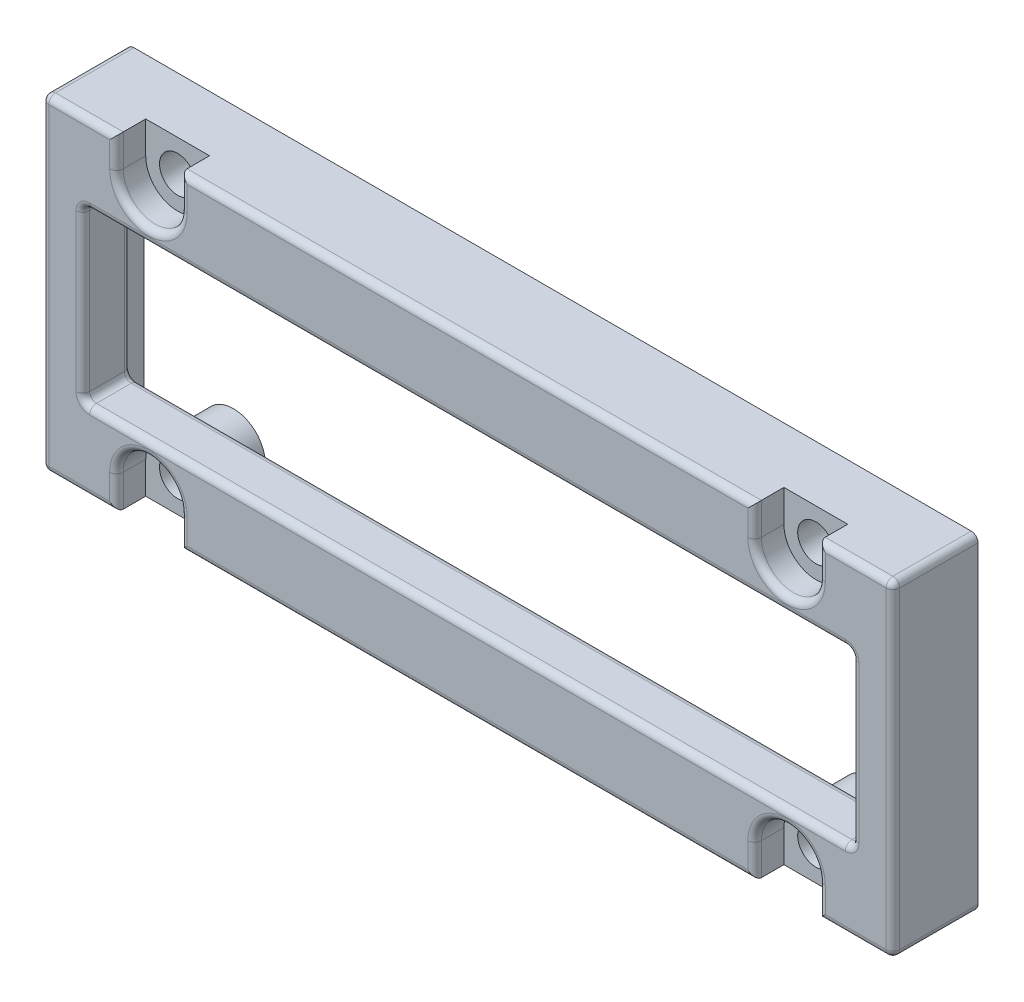
SolidWorks part; units mm, degrees
material "Nylon 101"
ref_plane "Front Plane" through (0, 0, 0) normal (0, 0, 1) x (1, 0, 0)
ref_plane "Top Plane" through (0, 0, 0) normal (0, 1, 0) x (1, 0, 0)
ref_plane "Right Plane" through (0, 0, 0) normal (1, 0, 0) x (0, 0, -1)
sketch "Sketch1" plane through (0, 0, 0) normal (0, 0, 1) x (1, 0, 0)
  line L1 (168.9878, -189.8186) -> (105.4878, -189.8186)
  line L2 (168.9878, -189.8186) -> (168.9878, -165.4346)
  line L3 (168.9878, -165.4346) -> (105.4878, -165.4346)
  line L4 (105.4878, -189.8186) -> (105.4878, -165.4346)
  line L5 (168.9878, -189.8186) -> (105.4878, -165.4346) construction
  line L6 (168.9878, -165.4346) -> (105.4878, -189.8186) construction
  point P4 (137.2378, -177.6266)
extrude "Boss-Extrude1" add sketch "Sketch1" along normal blind 6.35
hole_wizard "CBORE for #2 Socket Head Cap Screw1" positions "Sketch3" profile "Sketch2" counterbore size "#2" standard "ANSI Inch" end condition through all
sketch "Sketch3" plane through (0, 0, 6.35) normal (0, 0, 1) x (1, 0, 0)
  line L0 (163.0823, -187.7866) -> (161.0503, -187.7866) construction
  line L2 (161.0503, -189.8186) -> (161.0503, -165.4346) construction
  line L3 (105.4878, -189.8186) -> (168.9878, -189.8186) construction
  line L4 (168.9878, -165.4346) -> (105.4878, -165.4346) construction
  line L5 (161.0503, -177.6266) -> (168.9878, -177.6266) construction
  line L6 (168.9878, -189.8186) -> (168.9878, -165.4346) construction
  line L8 (137.2378, -189.8186) -> (137.2378, -165.4346) construction
  point P14 (161.0503, -187.431)
  point P26 (113.4253, -187.431)
  point P28 (161.0503, -167.8222)
  point P29 (113.4253, -167.8222)
  dimension "D1" = 2.3876
sketch "Sketch2" plane through (161.0503, -187.431, 6.35) normal (1, 0, 0) x (0, -1, 0)
  line L0 (0, 0) -> (0, 6.35)
  line L1 (0, 6.35) -> (1.3525, 6.35)
  line L3 (1.3525, 6.35) -> (1.3526, 2.1844)
  line L4 (1.3526, 2.1844) -> (2.3812, 2.1844)
  line L5 (2.3812, 2.1844) -> (2.3812, 0)
  line L7 (2.3812, 0) -> (0, 0)
  line L11 (0, -6.35) -> (0, 107.95) construction
  dimension "Thru Hole Dia." = 2.7051
  dimension "Thru Hole Depth" = 6.35
  dimension "C'Bore Dia." = 4.7625
  dimension "C'Bore Depth" = 2.1844
sketch "Sketch4" plane through (0, 0, 6.35) normal (0, 0, 1) x (1, 0, 0)
  line L1 (165.9398, -183.9766) -> (108.5358, -183.9766)
  line L2 (165.9398, -183.9766) -> (165.9398, -171.2766)
  line L3 (165.9398, -171.2766) -> (108.5358, -171.2766)
  line L4 (108.5358, -183.9766) -> (108.5358, -171.2766)
  line L5 (165.9398, -183.9766) -> (108.5358, -171.2766) construction
  line L6 (165.9398, -171.2766) -> (108.5358, -183.9766) construction
  point P4 (137.2378, -177.6266)
extrude "Cut-Extrude1" cut sketch "Sketch4" against normal through all
sketch "Sketch5" plane through (0, 0, 6.35) normal (0, 0, 1) x (1, 0, 0)
  line L0 (168.9878, -165.4346) -> (105.4878, -165.4346) construction
  line L1 (111.0441, -167.8222) -> (115.8066, -167.8222)
  line L2 (111.0441, -167.8222) -> (111.0441, -165.4346)
  line L3 (111.0441, -165.4346) -> (115.8066, -165.4346)
  line L4 (115.8066, -167.8222) -> (115.8066, -165.4346)
  line L5 (111.0441, -167.8222) -> (115.8066, -165.4346) construction
  line L6 (111.0441, -165.4346) -> (115.8066, -167.8222) construction
  line L7 (137.2378, -165.4346) -> (137.2378, -177.6266) construction
  line L8 (137.2378, -177.6266) -> (105.4878, -177.6266) construction
  line L9 (105.4878, -165.4346) -> (105.4878, -189.8186) construction
  line L10 (163.4316, -167.8222) -> (163.4316, -165.4346)
  line L11 (163.4316, -165.4346) -> (158.6691, -165.4346)
  line L12 (158.6691, -167.8222) -> (158.6691, -165.4346)
  line L13 (163.4316, -167.8222) -> (158.6691, -167.8222)
  line L14 (111.0441, -189.8186) -> (115.8066, -189.8186)
  line L15 (111.0441, -187.431) -> (111.0441, -189.8186)
  line L16 (111.0441, -187.431) -> (115.8066, -187.431)
  line L17 (115.8066, -187.431) -> (115.8066, -189.8186)
  line L18 (163.4316, -187.431) -> (158.6691, -187.431)
  line L19 (158.6691, -187.431) -> (158.6691, -189.8186)
  line L20 (163.4316, -189.8186) -> (158.6691, -189.8186)
  line L21 (163.4316, -187.431) -> (163.4316, -189.8186)
  circle A0 centre (113.4253, -167.8222) radius 2.3813 construction
  point P0 (113.4253, -167.8222)
  point P6 (113.4253, -166.6284)
  point P11 (113.4253, -167.8222)
extrude "Cut-Extrude2" cut sketch "Sketch5" against normal up to surface (2.1844 mm away) up to face at (114.7779, -167.8222, 4.1656)
sketch "Sketch7" plane through (0, 0, 0) normal (0, 0, -1) x (-1, 0, 0)
  line L0 (-163.4316, -167.8222) -> (-163.4316, -165.4346) construction
  line L1 (-158.6691, -165.4346) -> (-158.6691, -167.8222) construction
  line L2 (-115.8066, -167.8222) -> (-115.8066, -165.4346) construction
  line L3 (-111.0441, -165.4346) -> (-111.0441, -167.8222) construction
  line L4 (-111.0441, -187.431) -> (-111.0441, -189.8186) construction
  line L5 (-115.8066, -189.8186) -> (-115.8066, -187.431) construction
  line L6 (-158.6691, -187.431) -> (-158.6691, -189.8186) construction
  line L7 (-163.4316, -189.8186) -> (-163.4316, -187.431) construction
  line L8 (-163.4316, -167.8222) -> (-163.4316, -166.7046)
  line L9 (-158.6691, -166.7046) -> (-158.6691, -167.8222)
  line L10 (-115.8066, -167.8222) -> (-115.8066, -166.7046)
  line L11 (-111.0441, -166.7046) -> (-111.0441, -167.8222)
  line L12 (-111.0441, -187.431) -> (-111.0441, -188.5486)
  line L13 (-115.8066, -188.5486) -> (-115.8066, -187.431)
  line L14 (-158.6691, -187.431) -> (-158.6691, -188.5486)
  line L15 (-163.4316, -188.5486) -> (-163.4316, -187.431)
  line L20 (-168.9878, -165.4346) -> (-168.9878, -189.8186)
  line L21 (-168.9878, -189.8186) -> (-105.4878, -189.8186)
  line L22 (-105.4878, -189.8186) -> (-105.4878, -165.4346)
  line L23 (-105.4878, -165.4346) -> (-168.9878, -165.4346)
  line L24 (-168.9878, -165.4346) -> (-168.9878, -189.8186) construction
  line L25 (-168.9878, -189.8186) -> (-105.4878, -189.8186) construction
  line L26 (-105.4878, -189.8186) -> (-105.4878, -165.4346) construction
  line L27 (-105.4878, -165.4346) -> (-168.9878, -165.4346) construction
  line L28 (-106.7578, -166.7046) -> (-111.0441, -166.7046)
  line L29 (-167.7178, -166.7046) -> (-167.7178, -188.5486)
  line L30 (-167.7178, -188.5486) -> (-163.4316, -188.5486)
  line L31 (-106.7578, -188.5486) -> (-106.7578, -166.7046)
  line L32 (-165.9398, -183.9766) -> (-108.5358, -183.9766)
  line L33 (-165.9398, -171.2766) -> (-165.9398, -183.9766)
  line L34 (-108.5358, -171.2766) -> (-165.9398, -171.2766)
  line L35 (-108.5358, -183.9766) -> (-108.5358, -171.2766)
  line L36 (-165.9398, -183.9766) -> (-108.5358, -183.9766)
  line L37 (-165.9398, -171.2766) -> (-165.9398, -183.9766)
  line L38 (-108.5358, -171.2766) -> (-165.9398, -171.2766)
  line L39 (-108.5358, -183.9766) -> (-108.5358, -171.2766)
  line L40 (-163.4316, -166.7046) -> (-167.7178, -166.7046)
  line L41 (-106.7578, -166.7046) -> (-167.7178, -166.7046) construction
  line L42 (-115.8066, -166.7046) -> (-158.6691, -166.7046)
  line L43 (-111.0441, -188.5486) -> (-106.7578, -188.5486)
  line L44 (-167.7178, -188.5486) -> (-106.7578, -188.5486) construction
  line L45 (-158.6691, -188.5486) -> (-115.8066, -188.5486)
  arc A0 (-163.4316, -167.8222) -> (-158.6691, -167.8222) centre (-161.0503, -167.8222) ccw construction
  arc A1 (-115.8066, -167.8222) -> (-111.0441, -167.8222) centre (-113.4253, -167.8222) ccw construction
  arc A2 (-111.0441, -187.431) -> (-115.8066, -187.431) centre (-113.4253, -187.431) ccw construction
  arc A3 (-158.6691, -187.431) -> (-163.4316, -187.431) centre (-161.0503, -187.431) ccw construction
  arc A4 (-163.4316, -167.8222) -> (-158.6691, -167.8222) centre (-161.0503, -167.8222) ccw
  arc A5 (-115.8066, -167.8222) -> (-111.0441, -167.8222) centre (-113.4253, -167.8222) ccw
  arc A6 (-111.0441, -187.431) -> (-115.8066, -187.431) centre (-113.4253, -187.431) ccw
  arc A7 (-158.6691, -187.431) -> (-163.4316, -187.431) centre (-161.0503, -187.431) ccw
  dimension "D1" = 0
  dimension "D2" = 0
  dimension "D3" = 1.27
extrude "Cut-Extrude3" cut sketch "Sketch7" against normal offset from surface (2.7432 mm away) 1.4224 up to face at (162.4029, -187.431, 4.1656)
fillet "Fillet1" radius 0.508 68 edges at (137.2378, -171.2766, 6.35) (108.5358, -177.6266, 6.35) (137.2378, -183.9766, 6.35) (165.9398, -177.6266, 6.35) (137.2378, -189.8186, 6.35) (115.8066, -188.6248, 6.35) (113.4253, -185.0497, 6.35) (111.0441, -188.6248, 6.35) (108.2659, -189.8186, 6.35) (105.4878, -177.6266, 6.35) (108.2659, -165.4346, 6.35) (111.0441, -166.6284, 6.35) (113.4253, -170.2034, 6.35) (115.8066, -166.6284, 6.35) (137.2378, -165.4346, 6.35) (158.6691, -166.6284, 6.35) (161.0503, -170.2034, 6.35) (163.4316, -166.6284, 6.35) (166.2097, -165.4346, 6.35) (168.9878, -177.6266, 6.35) (166.2097, -189.8186, 6.35) (163.4316, -188.6248, 6.35) (161.0503, -185.0497, 6.35) (158.6691, -188.6248, 6.35) (165.9398, -177.6266, 2.7432) (137.2378, -183.9766, 2.7432) (108.5358, -177.6266, 2.7432) (137.2378, -171.2766, 2.7432) (158.6691, -167.2634, 2.7432) (137.2378, -166.7046, 2.7432) (115.8066, -167.2634, 2.7432) (113.4253, -170.2034, 2.7432) (111.0441, -167.2634, 2.7432) (108.9009, -166.7046, 2.7432) (106.7578, -177.6266, 2.7432) (108.9009, -188.5486, 2.7432) (111.0441, -187.9898, 2.7432) (113.4253, -185.0497, 2.7432) (115.8066, -187.9898, 2.7432) (137.2378, -188.5486, 2.7432) (158.6691, -187.9898, 2.7432) (161.0503, -185.0497, 2.7432) (163.4316, -187.9898, 2.7432) (165.5747, -188.5486, 2.7432) (167.7178, -177.6266, 2.7432) (165.5747, -166.7046, 2.7432) (163.4316, -167.2634, 2.7432) (161.0503, -170.2034, 2.7432) (168.9878, -165.4346, 3.175) (105.4878, -165.4346, 3.175) (105.4878, -189.8186, 3.175) (168.9878, -189.8186, 3.175) (165.9398, -171.2766, 4.5466) (165.9398, -183.9766, 4.5466) (108.5358, -183.9766, 4.5466) (108.5358, -171.2766, 4.5466) (158.6691, -166.7046, 1.3716) (115.8066, -166.7046, 1.3716) (111.0441, -166.7046, 1.3716) (106.7578, -166.7046, 1.3716) (106.7578, -188.5486, 1.3716) (111.0441, -188.5486, 1.3716) (115.8066, -188.5486, 1.3716) (158.6691, -188.5486, 1.3716) (163.4316, -188.5486, 1.3716) (167.7178, -166.7046, 1.3716) (163.4316, -166.7046, 1.3716) (167.7178, -188.5486, 1.3716)
